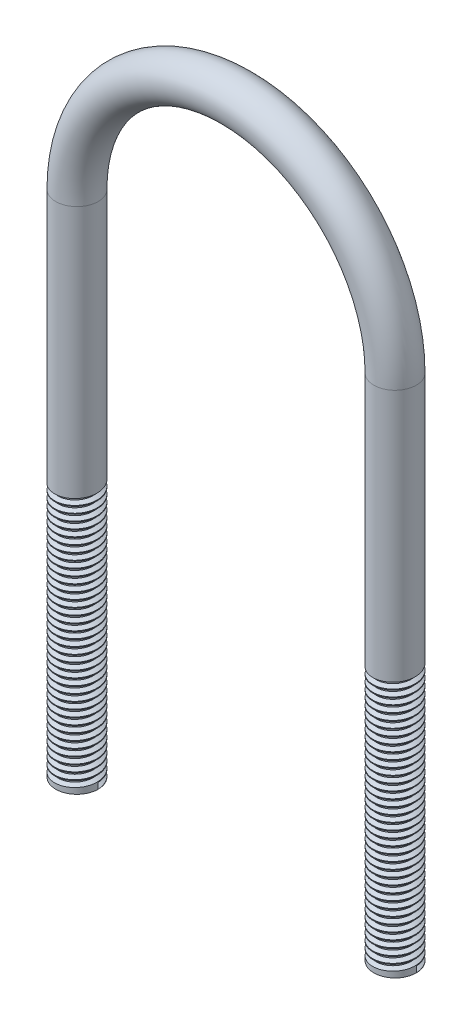
SolidWorks part; units mm, degrees
ref_plane "Front Plane" through (0, 0, 0) normal (0, 0, 1) x (1, 0, 0)
ref_plane "Top Plane" through (0, 0, 0) normal (0, 1, 0) x (1, 0, 0)
ref_plane "Right Plane" through (0, 0, 0) normal (1, 0, 0) x (0, 0, -1)
sketch "Sketch1" plane through (0, 0, 0) normal (0, 1, 0) x (1, 0, 0)
  circle A0 centre (-18.75, 0) radius 2.5
  circle A1 centre (18.75, 0) radius 2.5
  dimension "D1" = 5
  dimension "D2" = 5
  dimension "D3" = 18.75
  dimension "D4" = 18.75
extrude "Boss-Extrude1" add sketch "Sketch1" along normal blind 60
sketch "Sketch2" plane through (0, 60, 0) normal (0, 1, 0) x (1, 0, 0)
  circle A0 centre (-18.75, 0) radius 2.5
sketch "Sketch3" plane through (0, 0, 0) normal (0, 0, 1) x (1, 0, 0)
  line L0 (21.25, 60) -> (16.25, 60) construction
  arc A0 (18.75, 60) -> (-18.75, 60) centre (0, 60) ccw
  dimension "D1" = 37.5
  dimension "D2" = 0
sweep "Sweep1" add profiles "Sketch2" path "Sketch3"
thread "Thread1" pitch 0.8 method cut profile "Thread Profile1" start angle 0, offset 0, length 30, pitch 0.8, diameter 5
ref_plane "Plane1" through (-16.25, 0, 0) normal (0, 0, 1) x (1, 0, 0)
sketch "Thread Profile1" plane through (-16.25, 0, 0) normal (0, 0, 1) x (1, 0, 0)
  line L0 (0, 0) -> (0, 0.8) construction
  line L11 (0, 0) -> (0, 0.7)
  line L12 (0, 0.7) -> (-0.433, 0.45)
  line L13 (-0.433, 0.45) -> (-0.433, 0.25)
  line L15 (-0.433, 0.25) -> (0, 0)
  line L17 (-0.433, 0.35) -> (0, 0.35) construction
  point P2 (0, 0)
  dimension "Pitch" = 0.8
  dimension "Profile_Angle" = 60
  dimension "Profile_Land" = 0.2
  dimension "Profile_Height" = 0.433
thread "Thread2" pitch 0.8 method cut profile "Thread Profile2" start angle 0, offset 0, length 30, pitch 0.8, diameter 5
ref_plane "Plane2" through (21.25, 0, 0) normal (0, 0, 1) x (1, 0, 0)
sketch "Thread Profile2" plane through (21.25, 0, 0) normal (0, 0, 1) x (1, 0, 0)
  line L0 (0, 0) -> (0, 0.8) construction
  line L11 (0, 0) -> (0, 0.7)
  line L12 (0, 0.7) -> (-0.433, 0.45)
  line L13 (-0.433, 0.45) -> (-0.433, 0.25)
  line L15 (-0.433, 0.25) -> (0, 0)
  line L17 (-0.433, 0.35) -> (0, 0.35) construction
  point P2 (0, 0)
  dimension "Pitch" = 0.8
  dimension "Profile_Angle" = 60
  dimension "Profile_Land" = 0.2
  dimension "Profile_Height" = 0.433
